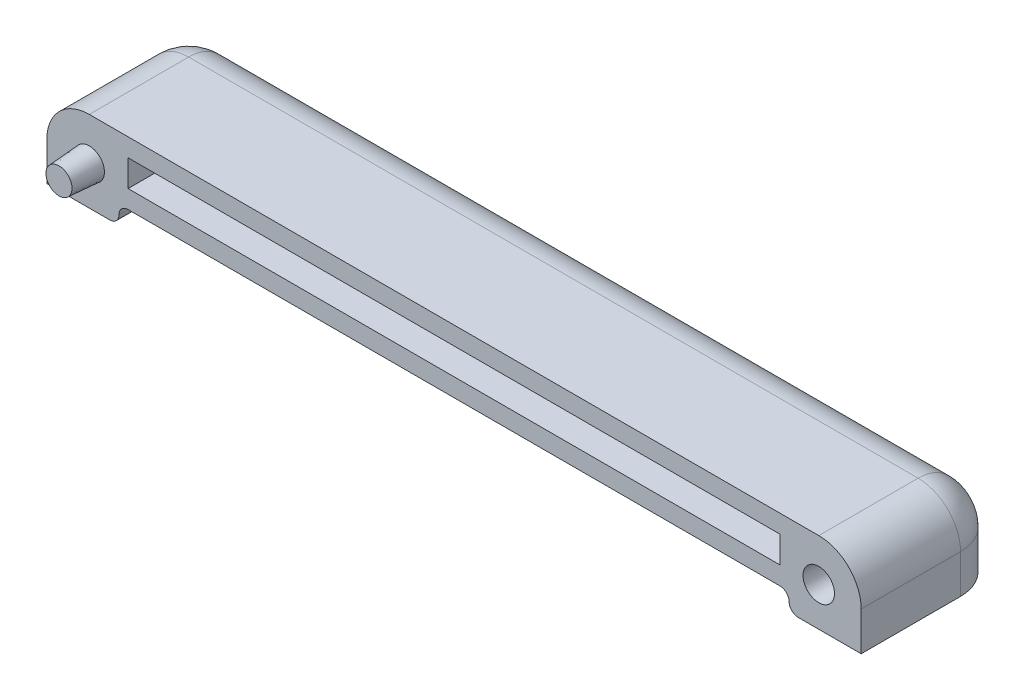
SolidWorks part; units mm, degrees
ref_plane "Спереди" through (0, 0, 0) normal (0, 0, 1) x (1, 0, 0)
ref_plane "Сверху" through (0, 0, 0) normal (0, 1, 0) x (1, 0, 0)
ref_plane "Справа" through (0, 0, 0) normal (1, 0, 0) x (0, 0, -1)
sketch "Sketch1" plane through (0, 0, 0) normal (0, 0, 1) x (1, 0, 0)
  line L0 (-67.2, -306.7486) -> (-67.2, -161.9486) construction
  line L5 (-60.2, -161.9486) -> (-43.8, -161.9486) construction
  line L6 (-43.6, -161.9486) -> (-43.6, -171.9486)
  line L7 (-43.6, -171.9486) -> (43.6, -171.9486)
  line L8 (43.6, -171.9486) -> (43.6, -161.9486)
  line L9 (43.6, -161.9486) -> (67.2, -161.9486)
  line L10 (67.2, -161.9486) -> (67.2, -148.5486)
  line L11 (67.2, -148.5486) -> (-67.2, -148.5486)
  line L12 (-67.2, -148.5486) -> (-67.2, -161.9486)
  line L13 (-67.2, -161.9486) -> (-43.6, -161.9486)
  line L16 (-43.8, -306.7486) -> (-43.8, -161.9486) construction
  point P10 (0, -148.5486)
  point P11 (0, -171.9486)
  dimension "D1" = 0.2
  dimension "D2" = 10
  dimension "D3" = 13.4
extrude "Extrude1" add sketch "Sketch1" along normal blind 3
sketch "Sketch3" plane through (0, 0, 3) normal (0, 0, 1) x (1, 0, 0)
  line L0 (-67.2, -148.5486) -> (-67.2, -161.9486) construction
  line L1 (67.2, -148.5486) -> (-67.2, -148.5486) construction
  line L2 (67.2, -161.9486) -> (67.2, -148.5486) construction
  line L3 (-67.2, -148.5486) -> (-67.2, -161.9486)
  line L4 (67.2, -148.5486) -> (-67.2, -148.5486)
  line L5 (67.2, -161.9486) -> (67.2, -148.5486)
  line L6 (67.2, -161.9486) -> (-67.2, -161.9486)
extrude "Extrude2" add sketch "Sketch3" along normal up to vertex (7.4 mm away)
sketch "Sketch4" plane through (0, 0, 10.4) normal (0, 0, 1) x (1, 0, 0)
  line L2 (53.8, -155.9486) -> (-53.8, -155.9486)
  line L3 (-53.8, -151.5486) -> (53.8, -151.5486)
  line L4 (-53.8, -155.9486) -> (-53.8, -151.5486)
  line L5 (-53.8, -151.5486) -> (-67.2, -151.5486) construction
  line L6 (-67.2, -148.5486) -> (-67.2, -161.9486) construction
  line L7 (67.2, -151.5486) -> (53.8, -151.5486) construction
  line L8 (67.2, -161.9486) -> (67.2, -148.5486) construction
  line L9 (53.8, -155.9486) -> (53.8, -151.5486)
  line L14 (67.2, -148.5486) -> (-67.2, -148.5486)
  line L15 (-67.2, -148.5486) -> (-67.2, -161.9486)
  line L16 (-67.2, -161.9486) -> (67.2, -161.9486)
  line L17 (67.2, -161.9486) -> (67.2, -148.5486)
  line L18 (67.2, -148.5486) -> (-67.2, -148.5486)
  line L19 (-67.2, -148.5486) -> (-67.2, -161.9486)
  line L20 (-67.2, -161.9486) -> (67.2, -161.9486)
  line L21 (67.2, -161.9486) -> (67.2, -148.5486)
  point P12 (0, -151.5486)
  point P13 (0, -148.5486)
  dimension "D2" = 3
  dimension "D3" = 4.4
  dimension "D4" = 13.4
extrude "Extrude3" add sketch "Sketch4" along normal up to vertex (13 mm away)
fillet "Fillet1" radius 7 5 edges at (0, -148.5486, 0) (67.2, -155.2486, 0) (67.2, -148.5486, 11.7) (-67.2, -155.2486, 0) (-67.2, -148.5486, 11.7)
sketch "Sketch6" plane through (0, -161.9486, 0) normal (0, -1, 0) x (1, 0, 0)
  line L0 (-55.3, 23.4) -> (-55.3, 18.9)
  line L1 (-67.2, 23.4) -> (67.2, 23.4) construction
  line L2 (-48.3, 11.9) -> (48.3, 11.9)
  line L3 (55.3, 18.9) -> (55.3, 23.4)
  line L5 (-56.8, 17.4) -> (-56.8, 23.4) construction
  line L6 (-55.3, 23.4) -> (55.3, 23.4)
  line L8 (-43.8, 10.4) -> (-49.8, 10.4) construction
  arc A0 (-48.3, 11.9) -> (-55.3, 18.9) centre (-48.3, 18.9) cw
  arc A1 (48.3, 11.9) -> (55.3, 18.9) centre (48.3, 18.9) ccw
  point P5 (0, 11.9)
  dimension "D1" = 7
  dimension "D2" = 7
  dimension "D3" = 1.5
  dimension "D4" = 1.5
extrude "Cut-Extrude1" cut sketch "Sketch6" against normal blind 3
fillet "Fillet2" radius 1.5 10 edges at (55.3, -158.9486, 21.15) (53.2497, -158.9486, 13.9503) (0, -158.9486, 11.9) (-53.2497, -158.9486, 13.9503) (-55.3, -158.9486, 21.15) (-55.3, -161.9486, 21.15) (-53.2497, -161.9486, 13.9503) (55.3, -161.9486, 21.15) (53.2497, -161.9486, 13.9503) (0, -161.9486, 11.9)
sketch "Sketch7" plane through (0, 0, 23.4) normal (0, 0, 1) x (1, 0, 0)
  circle A0 centre (-60.2, -155.5486) radius 2.5
  dimension "D1" = 5
extrude "Extrude4" add sketch "Sketch7" along normal blind 5 draft 4
sketch "Sketch8" plane through (0, 0, 23.4) normal (0, 0, 1) x (1, 0, 0)
  circle A0 centre (60.2, -155.5486) radius 2.6
  dimension "D1" = 5.2
extrude "Cut-Extrude2" cut sketch "Sketch8" against normal blind 5.2 draft 3.8
equation "\"pin_l\"=5"
equation "\"pin_skew\"=4"
equation "\"pin_r\"=5"
equation "\"thickness\"=4"
equation "\"M4_plastic_thread\"=3.8"
equation "\"M3_plastic_thread\" = 2.8"
equation "\"D3@Sketch1\"=\"thickness\"+9.4"
equation "\"D3@Sketch4\"=\"thickness\"+0.4"
equation "\"D4@Sketch4\"=\"thickness\"+9.4"
equation "\"D1@Sketch7\"=\"pin_r\""
equation "\"D1@Extrude4\"=\"pin_l\""
equation "\"D3@Extrude4\"=\"pin_skew\""
equation "\"D1@Sketch8\"=\"pin_r\"+0.2"
equation "\"D1@Cut-Extrude2\"=\"pin_l\"+0.2"
equation "\"D3@Cut-Extrude2\"=\"pin_skew\"-0.2"
